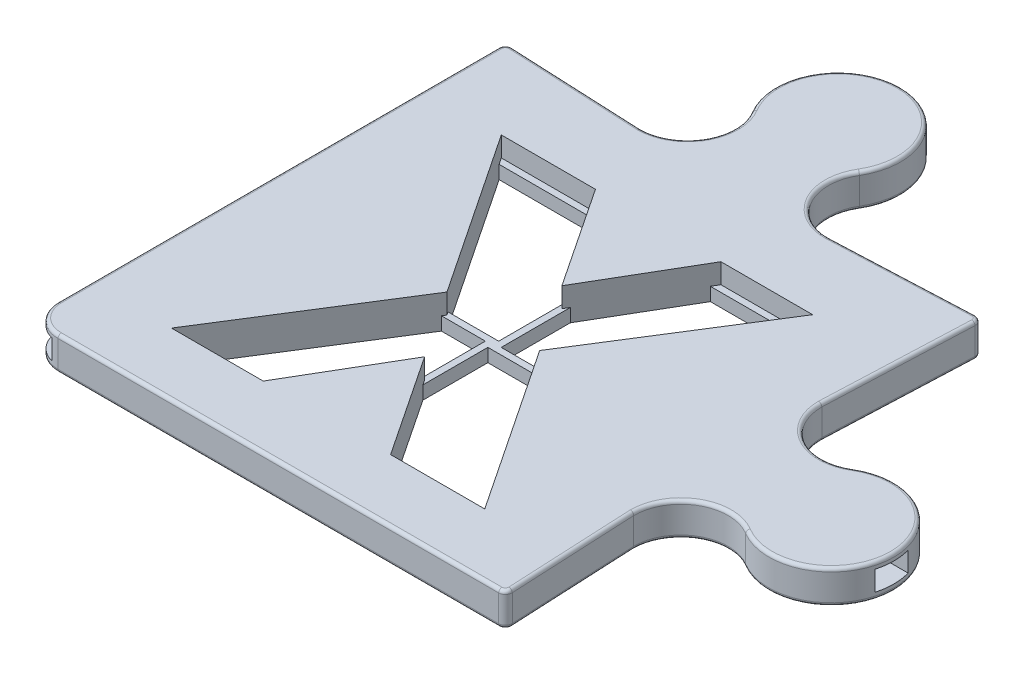
SolidWorks part; units mm, degrees
ref_plane "Front Plane" through (0, 0, 0) normal (0, 0, 1) x (1, 0, 0)
ref_plane "Top Plane" through (0, 0, 0) normal (0, 1, 0) x (1, 0, 0)
ref_plane "Right Plane" through (0, 0, 0) normal (1, 0, 0) x (0, 0, -1)
sketch "Sketch1" plane through (0, 0, 0) normal (0, 1, 0) x (1, 0, 0)
  line L0 (-31, -36) -> (37, -36) construction
  line L1 (-36, 37) -> (-36, -31) construction
  line L2 (-14.1421, 36) -> (-36, 37) construction
  line L3 (37, 37) -> (14.1421, 36) construction
  line L4 (36, 13.1421) -> (37, 37) construction
  line L5 (37, -36) -> (36, -15.1421) construction
  line L6 (-35.4, 36.3719) -> (-35.4, -31)
  line L7 (-36, 36) -> (36, 36) construction
  line L8 (-36, 36) -> (-36, -36) construction
  line L9 (-36, -36) -> (36, -36) construction
  line L10 (36, 36) -> (36, -36) construction
  line L11 (-31, -35.4) -> (36.3705, -35.4)
  line L12 (36.3705, -35.4) -> (35.4, -15.1568)
  line L13 (35.4, 13.155) -> (36.3732, 36.372)
  line L14 (36.3732, 36.372) -> (14.1555, 35.4)
  line L15 (-14.1562, 35.4) -> (-35.4, 36.3719)
  line L16 (-30, -24) -> (30, -24) construction
  line L17 (-30, 29) -> (30, 29) construction
  line L18 (-30, 29) -> (-30, -31) construction
  line L19 (-30, -31) -> (30, -31) construction
  line L20 (30, 29) -> (30, -31) construction
  line L21 (-30, 24) -> (30, 24) construction
  line L22 (-30, 24) -> (-30, -26) construction
  line L23 (-30, -26) -> (30, -26) construction
  line L24 (30, 24) -> (30, -26) construction
  arc A0 (-36, -31) -> (-31, -36) centre (-31, -31) ccw construction
  arc A1 (-14.1421, 36) -> (-8.571, 45.8485) centre (-14.1421, 42.5) ccw construction
  arc A2 (8.571, 45.8485) -> (-8.571, 45.8485) centre (0, 51) ccw construction
  arc A3 (8.571, 45.8485) -> (14.1421, 36) centre (14.1421, 42.5) ccw construction
  arc A4 (36, 13.1421) -> (45.8485, 7.571) centre (42.5, 13.1421) ccw construction
  arc A5 (45.8485, -9.571) -> (45.8485, 7.571) centre (51, -1) ccw construction
  arc A6 (45.8485, -9.571) -> (36, -15.1421) centre (42.5, -15.1421) ccw construction
  arc A7 (-35.4, -31) -> (-31, -35.4) centre (-31, -31) ccw
  arc A8 (46.1576, -9.0567) -> (35.4, -15.1568) centre (42.5, -15.1421) ccw
  arc A9 (46.1576, -9.0567) -> (46.1576, 7.0567) centre (51, -1) ccw
  arc A10 (35.4, 13.155) -> (46.1576, 7.0567) centre (42.5, 13.1421) ccw
  arc A11 (8.0567, 46.1576) -> (14.1555, 35.4) centre (14.1421, 42.5) ccw
  arc A12 (8.0567, 46.1576) -> (-8.0567, 46.1576) centre (0, 51) ccw
  arc A13 (-14.1562, 35.4) -> (-8.0567, 46.1576) centre (-14.1421, 42.5) ccw
  point P32 (36, 0)
  point P34 (0, 36)
  dimension "D5" = 6.5
  dimension "D6" = 10
  dimension "D7" = 6.5
  dimension "D13" = 5
  dimension "D9" = 10
  dimension "D11" = 6.5
  dimension "D12" = 6.5
  dimension "D1" = 72
  dimension "D2" = 1
  dimension "D3" = 1
  dimension "D4" = 15
  dimension "D8" = 1
  dimension "D10" = 35
  dimension "D14" = 15
  dimension "D15" = 36
  dimension "D16" = 1
  dimension "D18" = 60
  dimension "D19" = 60
  dimension "D20" = 5
  dimension "D21" = 6
  dimension "D22" = 5
  dimension "D23" = 50
  dimension "D24" = 2
  dimension "D17" = 0.6
extrude "Boss-Extrude1" add sketch "Sketch1" along normal blind 5
sketch "Sketch6" plane through (0, 0, 0) normal (0, -1, 0) x (1, 0, 0)
  line L0 (-35.4, -36.3719) -> (-35.4, 31) construction
  line L1 (-35.4, 17.9) -> (-27.4, 17.9)
  line L2 (-35.4, 17.9) -> (-35.4, -16.1)
  line L3 (-35.4, -16.1) -> (-27.4, -16.1)
  line L4 (-27.4, 17.9) -> (-27.4, -16.1)
  line L5 (-31, 35.4) -> (36.3705, 35.4) construction
  line L6 (-35.4, 14.65) -> (-30.4, 14.65)
  line L7 (-35.4, 14.65) -> (-35.4, -12.85)
  line L8 (-35.4, -12.85) -> (-30.4, -12.85)
  line L9 (-30.4, 14.65) -> (-30.4, -12.85)
  point P15 (-27.4, 0.9)
  point P16 (-30.4, 0.9)
  line M28 (-35.4, 31) -> (-35.4, -36.3719)
  dimension "D1" = 8
  dimension "D2" = 20.75
  dimension "D3" = 27.5
  dimension "D4" = 5
  dimension "D5" = 34
extrude "Cut-Extrude3" cut sketch "Sketch6" against normal blind 3 from offset 1 contours L6 L9 L8 L3 L4 L1 M28 | L9 L6 L2 L8 region at (-29.8665, 0, 0.9) region at (-32.9, 0, 0.9) offset against normal yes
extrude "Cut-Extrude4" cut sketch "Sketch6<3>" against normal up to next contours L9 L6 L2 L8 region at (-32.9, 0, 0.9)
sketch "Sketch6<3>" plane through (0, 0, 0) normal (0, -1, 0) x (1, 0, 0) same geometry as "Sketch6"
sketch "Sketch8" plane through (0, 0, 0) normal (0, -1, 0) x (1, 0, 0)
  line L1 (-2.5, -51.4) -> (2.5, -51.4)
  line L2 (-2.5, -51.4) -> (-2.5, -60.4)
  line L3 (-2.5, -60.4) -> (2.5, -60.4)
  line L4 (2.5, -51.4) -> (2.5, -60.4)
  line L5 (51.4, 3.5) -> (60.4, 3.5)
  line L6 (51.4, 3.5) -> (51.4, -1.5)
  line L7 (51.4, -1.5) -> (60.4, -1.5)
  line L8 (60.4, 3.5) -> (60.4, -1.5)
  arc A0 (-8.0567, -46.1576) -> (8.0567, -46.1576) centre (0, -51) ccw construction
  arc A1 (46.1576, -7.0567) -> (46.1576, 9.0567) centre (51, 1) ccw construction
  point P4 (0, -60.4)
  point P13 (60.4, 1)
  dimension "D1" = 5
  dimension "D2" = 9
  dimension "D3" = 5
  dimension "D4" = 9
extrude "Cut-Extrude5" cut sketch "Sketch8" against normal blind 3 from offset 1 offset against normal yes
sketch "Sketch9" plane through (0, 0, 0) normal (0, -1, 0) x (1, 0, 0)
  line L0 (-31, 35.4) -> (36.3705, 35.4) construction
  line L1 (-35.4, 14.65) -> (-35.4, 31) construction
  line L2 (-31.7636, 35.3332) -> (-35.4, 31) construction
  line L3 (-33.2571, 29.735) -> (-30.0429, 33.565) construction
  line L4 (-30.0429, 33.565) -> (-33.2571, 29.735) construction
  line L5 (-30.0429, 33.565) -> (-32.7119, 35.8048)
  line L6 (-33.2571, 29.735) -> (-35.926, 31.9747)
  line L7 (-32.7119, 35.8048) -> (-35.926, 31.9747)
  circle A0 centre (-31.65, 31.65) radius 2.5
  arc A1 (-31, 35.4) -> (-35.4, 31) centre (-31, 31) ccw construction
  arc M41 (-31, 35.4) -> (-35.4, 31) centre (-31, 31) ccw
  dimension "D1" = 5
  dimension "D3" = 3.75
  dimension "D4" = 5.6569
  dimension "D2" = 3.75
extrude "Cut-Extrude6" cut sketch "Sketch9" against normal blind 3 from offset 1 contours A0 L5 L6 M41 | A0 L5 region at (-33.6239, 0, 33.3064) region at (-31.65, 0, 31.65) offset against normal yes
sketch "Sketch11" plane through (-35.4, 0, 0) normal (-1, 0, 0) x (0, 0, 1)
  line L0 (-13.155, 0) -> (-36.372, 0) construction
  line L1 (-25.1, 3) -> (-19.1, 3)
  line L2 (-25.1, 3) -> (-25.1, 1.5)
  line L3 (-25.1, 1.5) -> (-19.1, 1.5)
  line L4 (-19.1, 3) -> (-19.1, 1.5)
  line L5 (-16.1, 4) -> (-16.1, 1) construction
  line L6 (35.4, 0) -> (15.1568, 0) construction
  line L7 (20.9, 3) -> (26.9, 3)
  line L8 (20.9, 3) -> (20.9, 1.5)
  line L9 (20.9, 1.5) -> (26.9, 1.5)
  line L10 (26.9, 3) -> (26.9, 1.5)
  line L12 (17.9, 4) -> (17.9, 1) construction
  dimension "D1" = 3
  dimension "D2" = 1.5
  dimension "D3" = 3
  dimension "D4" = 6
  dimension "D5" = 3
  dimension "D6" = 1.5
  dimension "D7" = 6
  dimension "D8" = 3
fillet "Fillet1" radius 0.5 17 edges at (-35.4, 0, 22.825) (-34.1113, 0, 34.1113) (2.6853, 0, 35.4) (35.8853, 0, 25.2784) (38.9978, 0, 8.966) (60.4, 0, 1) (38.9986, 0, -6.9655) (35.8866, 0, -24.7635) (25.2643, 0, -35.886) (7.9657, 0, -38.9984) (0, 0, -60.4) (-7.9658, 0, -38.9981) (-24.7781, 0, -35.886) (-35.4, 0, -24.611) (-32.9, 0, -12.85) (-30.4, 0, 0.9) (-32.9, 0, 14.65)
fillet "Fillet2" radius 0.5 13 edges at (-7.9658, 5, -38.9981) (0, 5, -60.4) (7.9657, 5, -38.9984) (25.2643, 5, -35.886) (35.8866, 5, -24.7635) (38.9986, 5, -6.9655) (60.4, 5, 1) (38.9978, 5, 8.966) (35.8853, 5, 25.2784) (2.6853, 5, 35.4) (-34.1113, 5, 34.1113) (-35.4, 5, -2.686) (-24.7781, 5, -35.886)
fillet "Fillet3" radius 1 9 edges at (36.2202, 0.1464, -36.2187) (36.2202, 4.8536, -36.2187) (36.3732, 2.5, -36.372) (-35.2536, 0.1464, -36.2186) (-35.2536, 4.8536, -36.2186) (36.2169, 0.1464, 35.2536) (36.2169, 4.8536, 35.2536) (36.3705, 2.5, 35.4) (-35.4, 2.5, -36.3719)
extrude "Cut-Extrude9" cut sketch "Sketch11" against normal blind 3
chamfer "Chamfer1" distance 1 angle 50 2 edges at (-35.4, 1.5, 23.9) (-35.4, 1.5, -22.1) first distance on face at (-35.4, 2.25, -22.1)
sketch "Sketch12" plane through (0, 5, 0) normal (0, 1, 0) x (1, 0, 0)
  text T0 "X" font "Poppins" height 50
extrude "Cut-Extrude10" cut sketch "Sketch12" against normal through all
sketch "Sketch13" plane through (0, 0, 0) normal (0, -1, 0) x (1, 0, 0)
  line L0 (-23.3306, 26) -> (-7.296, 0.5672) construction
  line L1 (-7.6201, 1.0812) -> (-1.0041, 1.0812)
  line L2 (-7.6201, 1.0812) -> (-7.6201, 0.0812)
  line L3 (-7.6201, 0.0812) -> (0.0037, 0.0812)
  line L5 (23.1863, -24) -> (7.3063, 1.2164) construction
  line L6 (-0.5359, 10.6867) -> (-9.5115, 26) construction
  line L11 (0.5359, -8.9031) -> (9.3673, -24) construction
  line L12 (9.6558, 26) -> (-0.5359, 10.6867) construction
  line L13 (-8.9254, 25) -> (-23.3306, 25)
  line L14 (-8.9254, 25) -> (-8.9254, 26)
  line L15 (-8.9254, 26) -> (-23.3306, 26)
  line L16 (-23.3306, 25) -> (-23.3306, 26)
  line L17 (8.9903, 25) -> (23.8252, 25)
  line L18 (8.9903, 25) -> (8.9903, 26)
  line L19 (8.9903, 26) -> (23.8252, 26)
  line L20 (23.8252, 25) -> (23.8252, 26)
  line L21 (-9.5115, -24) -> (0.5359, -8.9031) construction
  line L22 (-8.846, -23) -> (-23.681, -23)
  line L23 (-8.846, -23) -> (-8.846, -24)
  line L24 (-8.846, -24) -> (-23.681, -24)
  line L25 (-23.681, -23) -> (-23.681, -24)
  line L26 (-7.296, 0.5672) -> (-23.681, -24) construction
  line L27 (8.7823, -23) -> (23.1863, -23)
  line L28 (8.7823, -23) -> (8.7823, -24)
  line L29 (8.7823, -24) -> (23.1863, -24)
  line L30 (23.1863, -23) -> (23.1863, -24)
  line L31 (7.3063, 1.2164) -> (23.8252, 26) construction
  line L32 (0.0037, -9.7028) -> (1.0037, -9.7028)
  line L33 (0.0037, -9.7028) -> (0.0037, 0.0812)
  line L35 (1.0037, -9.7028) -> (1.0037, 0.0812)
  line L36 (-1.0041, 11.4857) -> (-0.0041, 11.4857)
  line L37 (-1.0041, 11.4857) -> (-1.0041, 1.0812)
  line L39 (-0.0041, 11.4857) -> (-0.0041, 1.7022)
  line L40 (7.6301, 1.7022) -> (-0.0041, 1.7022)
  line L41 (7.6301, 1.7022) -> (7.6301, 0.7022)
  line L42 (7.6301, 0.7022) -> (1.0037, 0.7022)
  line L43 (-1.0041, 1.7022) -> (-1.0041, 1.0812)
  line L44 (1.0037, 0.0812) -> (1.0037, 0.7022)
  line L45 (1.0037, 0.7022) -> (7.6301, 0.7022)
  line L46 (0.0037, 0.0812) -> (-7.6201, 0.0812)
  line M45 (9.6558, 26) -> (23.8252, 26)
  line M46 (23.8252, 26) -> (7.3063, 1.2164)
  line M47 (7.3063, 1.2164) -> (23.1863, -24)
  line M48 (23.1863, -24) -> (9.3673, -24)
  line M49 (9.3673, -24) -> (0.5359, -8.9031)
  line M50 (0.5359, -8.9031) -> (-9.5115, -24)
  line M51 (-9.5115, -24) -> (-23.681, -24)
  line M52 (-23.681, -24) -> (-7.296, 0.5672)
  line M53 (-7.296, 0.5672) -> (-23.3306, 26)
  line M55 (-9.5115, 26) -> (-0.5359, 10.6867)
  line M56 (-0.5359, 10.6867) -> (9.6558, 26)
  dimension "D1" = 1
  dimension "D2" = 1
  dimension "D3" = 1
  dimension "D4" = 1
  dimension "D5" = 0.621
  dimension "D6" = 0.621
  dimension "D7" = 1
  dimension "D8" = 1
  dimension "D9" = 1
  dimension "D10" = 1
extrude "Boss-Extrude2" add sketch "Sketch13" against normal blind 2 contours L35 L44 L42 L40 L39 L37 L1 L3 L33 M47 M46 M56 M55 M53 M52 M50 M49 | L17 M56 M46 M45 | L27 M49 M48 M47 | L22 M50 M52 M51 | L13 L16 L15 L14 region at (0.002, 0, 0.8918) region at (-16.2631, 0, -23.5) region at (16.4075, 0, 25.5) region at (15.9733, 0, -23.5003)
